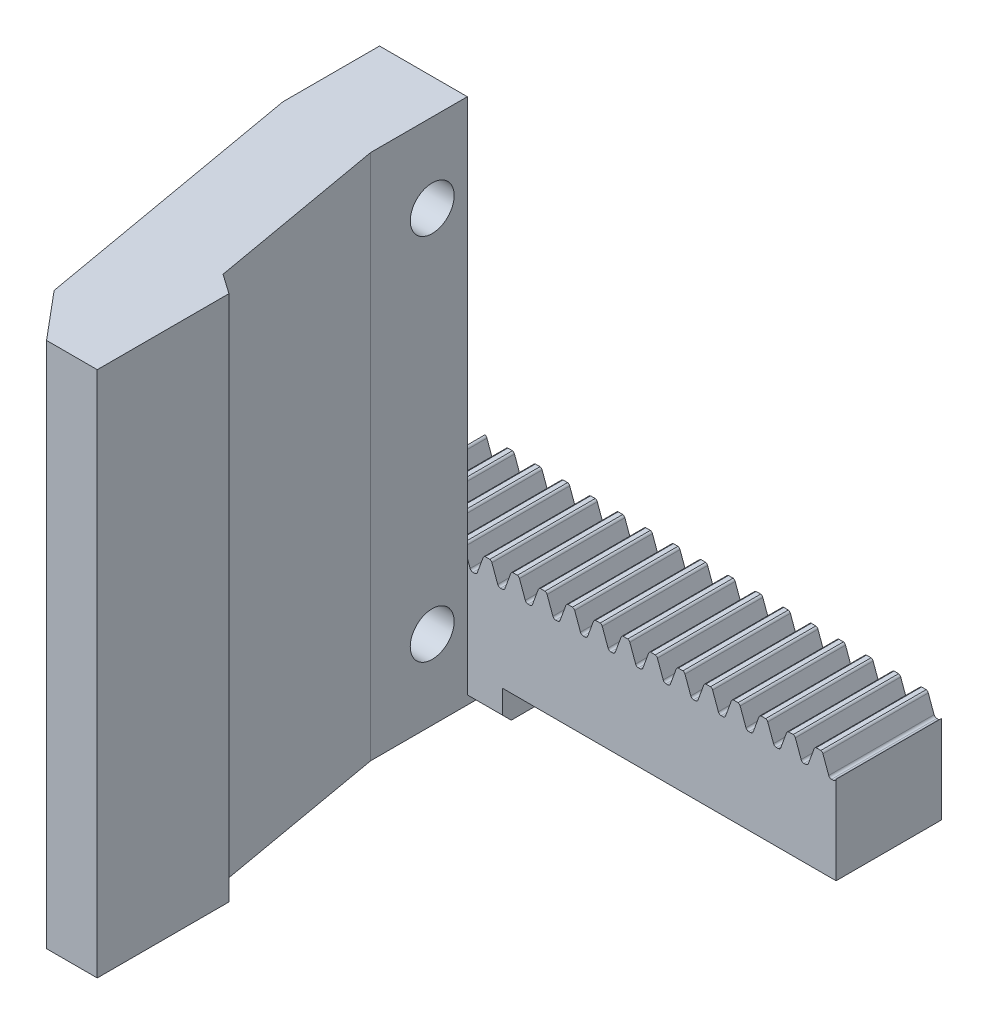
SolidWorks part; units mm, degrees
other "Markup1"
sketch "Sketch7" plane through (-50, -9.66, 16) normal (-0.9886, -0.1404, 0.0537) x (0.0542, 0, 0.9985)
ref_plane "Front Plane" through (0, 0, 0) normal (0, 0, 1) x (1, 0, 0)
ref_plane "Top Plane" through (0, 0, 0) normal (0, 1, 0) x (1, 0, 0)
ref_plane "Right Plane" through (0, 0, 0) normal (1, 0, 0) x (0, 0, -1)
sketch "Sketch1" plane through (0, 0, 0) normal (0, 0, 1) x (1, 0, 0)
  line L0 (-50, 6) -> (-50, -6) construction
  line L1 (-50, -6) -> (50, -6) construction
  line L2 (50, -6) -> (50, 6) construction
  line L4 (0, 6) -> (0, -6) construction
  line L5 (-50, 5) -> (50, 5) construction
  line L6 (-47.5453, 6) -> (-46.7025, 6) construction
  line L7 (-46.7025, 6) -> (-45.8835, 3.75) construction
  line L8 (-47.5453, 6) -> (-48.3643, 3.75) construction
  line L9 (-48.3643, 3.75) -> (-45.8835, 3.75) construction
  line L10 (-47.1239, 6) -> (-47.1239, 3.75) construction
  line L11 (-50, 0) -> (-40.8407, 0) construction
  line L12 (50, 0) -> (40.8407, 0) construction
  point P15 (-43.9823, 6)
  point P16 (-15.5, -6)
  point P17 (-46.3385, 5)
  point P18 (-47.9093, 5)
  point P21 (-0.5, -6)
  dimension "Length" = 100
  dimension "Height" = 12
  dimension "Approximate Number of Teeth" = 31
  dimension "Pressure Angle" = 20
  dimension "Circular Pitch" = 3.1416
  dimension "Addendum" = 1
  dimension "Dedendum" = 1.25
  dimension "Circular Tooth Thickness" = 1.5708
  dimension "Module" = 1
  dimension "Rack Length" = 94.2478
  dimension "D1" = 6.2832
sketch "Sketch2" plane through (0, 0, 0) normal (1, 0, 0) x (0, 0, -1)
  line L0 (-6, 0) -> (6, 0) construction
  dimension "Face Width" = 12
sketch "Sketch3" plane through (0, 0, 0) normal (0, 0, 1) x (1, 0, 0)
  line L1 (-50, 6) -> (50, 6)
  line L2 (-50, 6) -> (-50, -6)
  line L3 (-50, -6) -> (50, -6)
  line L4 (50, 6) -> (50, -6)
extrude "Boss-Extrude1" add sketch "Sketch3" against normal up to vertex (6 mm away) and the other way up to vertex (6 mm away) up to point (0, 0, -6) other way up to point (0, 0, 6)
sketch "Sketch4" plane through (0, 0, 0) normal (0, 0, 1) x (1, 0, 0)
  line L0 (-47.1239, 6) -> (-43.9823, 6) construction
  line L9 (-45.5531, 6) -> (-45.5531, 3.75)
  line L10 (-45.5531, 3.75) -> (-45.8835, 3.75)
  line L11 (-45.8835, 3.75) -> (-46.7025, 6)
  line L12 (-46.7025, 6) -> (-45.5531, 6)
  line L13 (-47.5453, 6) -> (-48.3643, 3.75)
  line L14 (-48.3643, 3.75) -> (-48.6947, 3.75)
  line L15 (-48.6947, 3.75) -> (-48.6947, 6)
  line L16 (-48.6947, 6) -> (-47.5453, 6)
  line L17 (50, 6) -> (-50, 6) construction
  line L18 (-47.5453, 6) -> (-47.3104, 6)
  line L19 (-46.9374, 6) -> (-46.7025, 6)
  arc A0 (-48.5992, 3.75) -> (-48.2839, 3.9708) centre (-48.5992, 4.0855) ccw
  arc A1 (-45.9639, 3.9708) -> (-45.6486, 3.75) centre (-45.6486, 4.0855) ccw
  arc A2 (-47.6257, 5.7792) -> (-47.3104, 6) centre (-47.3104, 5.6645) cw
  arc A3 (-46.9374, 6) -> (-46.6221, 5.7792) centre (-46.9374, 5.6645) cw
  dimension "D1" = 0.3355
extrude "Cut-Extrude1" cut sketch "Sketch4" against normal through all both and the other way through all contours L14 A0 L13 L16 L15 | L13 A2 L18 | L19 A3 L11 | L11 A1 L10 L9 L12 region at (-45.9615, 5.0903, 0) region at (-46.7355, 5.9529, 0) region at (-47.5123, 5.9529, 0) region at (-48.2863, 5.0903, 0)
pattern_linear "LPattern1" count 32 spacing 3.1416 along (1, 0, 0) count 2 spacing 3.1416 along (-1, 0, 0) of "Cut-Extrude1"
sketch "Drawing Refernce 1" plane through (0, 0, 6) normal (0, 0, 1) x (1, 0, 0)
  line L0 (-50, 0) -> (50, 0) construction
  point P6 (-35, 0)
  point P7 (-27.5, 0)
  point P8 (35, 0)
  dimension "D1" = 15
  dimension "D2" = 22.5
  dimension "D3" = 15
sketch "Sketch5" plane through (0, 0, 6) normal (0, 0, 1) x (1, 0, 0)
  line L0 (2, -6) -> (2, 23.2722) construction
  line L1 (-50, -6) -> (50, -6) construction
  line L2 (-50, 5.9906) -> (-50, -6) construction
  line L8 (2, -6) -> (50.3789, -6)
  line L9 (2, -6) -> (2, 6.3802)
  line L10 (2, 6.3802) -> (50.3789, 6.3802)
  line L11 (50.3789, -6) -> (50.3789, 6.3802)
  dimension "D1" = 52
extrude "Cut-Extrude2" cut sketch "Sketch5" against normal through all
sketch "Sketch6" plane through (0, 0, 6) normal (0, 0, 1) x (1, 0, 0)
  line L0 (-50, -6) -> (2, -6) construction
  line L1 (-50, -9.66) -> (-40, -9.66)
  line L2 (-50, -9.66) -> (-50, 50.34)
  line L3 (-50, 50.34) -> (-40, 50.34)
  line L4 (-40, -9.66) -> (-40, 50.34)
  line L5 (-50, 5.9906) -> (-50, -6) construction
  dimension "D1" = 10
  dimension "D2" = 3.66
  dimension "D3" = 60
extrude "Boss-Extrude2" add sketch "Sketch6" along normal blind 8
sketch "Sketch8" plane through (-50, 0, 0) normal (-1, 0, 0) x (0, 0, 1)
  line L1 (14, 50.34) -> (14, -9.66) construction
  line L2 (14, -9.66) -> (6, -9.66) construction
  line L3 (14, 50.34) -> (6, 50.34) construction
  circle A0 centre (10, 41.34) radius 2.5
  circle A1 centre (10, -0.66) radius 2.5
  dimension "D1" = 5
  dimension "D2" = 5
  dimension "D3" = 4
  dimension "D4" = 4
  dimension "D5" = 9
  dimension "D6" = 9
extrude "Cut-Extrude3" cut sketch "Sketch8" against normal through all
sketch "Sketch9" plane through (0, 0, 14) normal (0, 0, 1) x (1, 0, 0)
  line L0 (-40, -9.66) -> (-40, 50.34) construction
  line L1 (-50, 50.34) -> (-38.86, 50.34)
  line L2 (-50, 50.34) -> (-50, -9.66)
  line L3 (-50, -9.66) -> (-38.86, -9.66)
  line L4 (-38.86, 50.34) -> (-38.86, -9.66)
  dimension "D1" = 1.14
extrude "Boss-Extrude3" add sketch "Sketch9" along normal blind 40
sketch "Sketch10" plane through (0, -9.66, 0) normal (0, -1, 0) x (1, 0, 0)
  line L0 (-50, 44) -> (-38.86, 44) construction
  line L1 (-50, 54) -> (-50, 6) construction
  line L2 (-38.86, 54) -> (-38.86, 14) construction
  line L3 (-50, 54) -> (-38.86, 54) construction
  line L5 (-38.86, 44) -> (-38.86, 14)
  line L6 (-38.86, 14) -> (-40, 14)
  line L7 (-40, 14) -> (-40, 44)
  line L8 (-40, 44) -> (-38.86, 44)
  dimension "D1" = 10
extrude "Cut-Extrude4" cut sketch "Sketch10" against normal through all both
chamfer "Chamfer1" distance 12 angle 45 1 edges at (-45, -6, 6)
sketch "Sketch11" plane through (-50, 0, 0) normal (-1, 0, 0) x (0, 0, 1)
  line L5 (-2.34, -9.66) -> (-6, -6)
  line L6 (-6, -6) -> (-6, 5.9906)
  line L7 (-6, 5.9906) -> (6, 5.9906)
  line L8 (6, 5.9906) -> (6, 50.34)
  line L9 (48.3431, 50.34) -> (54, 44.6831)
  line L10 (54, -4.0031) -> (48.3431, -9.66)
  line L11 (43.5443, -10.137) -> (43.4726, -9.66)
  line L12 (-2.34, -9.66) -> (48.3431, -9.66)
  line L13 (6, 50.34) -> (48.3431, 50.34)
  line L14 (54, 44.6831) -> (54, -4.0031)
  circle M13 centre (10, 41.34) radius 2.5
  circle M14 centre (10, -0.66) radius 2.5
  line M15 (6, 5.9906) -> (-6, 5.9906)
  line M16 (-6, 5.9906) -> (-6, -6)
  line M17 (-6, -6) -> (-2.34, -9.66)
  line M18 (-2.34, -9.66) -> (54, -9.66)
  line M19 (54, -9.66) -> (54, 50.34)
  line M20 (54, 50.34) -> (6, 50.34)
  line M21 (6, 50.34) -> (6, 5.9906)
  dimension "D3" = 8
extrude "Cut-Extrude7" cut sketch "Sketch11" against normal blind 71 flip side to cut contours L10 L9 M19 M20 M21 M15 M16 M17 M18 M14 M13 region at (-50, 19.0116, 28.2195)
sketch "Sketch12" plane through (-40, 0, 0) normal (1, 0, 0) x (0, 0, -1)
  line L0 (-54, 44.6831) -> (-54, -9.66)
  line L1 (-44, 50.34) -> (-6, 50.34) construction
  line L2 (-17, 50.34) -> (-17, -9.66)
  line L3 (-44, -9.66) -> (2.34, -9.66) construction
  line L4 (-54, 50.34) -> (-17, 50.34)
  line L5 (-54, 44.6831) -> (-54, 50.34)
  line L7 (-54, -9.66) -> (-17, -9.66)
extrude "Cut-Extrude8" cut sketch "Sketch12" against normal blind 30 and the other way blind 30
sketch "Sketch13" plane through (0, -9.66, 0) normal (0, -1, 0) x (1, 0, 0)
  line L1 (-40, 17) -> (-36.3987, 37.4238)
  line L5 (-50, 17) -> (-40, 17)
  line L6 (-50, 17) -> (-44.4214, 48.6377)
  line L7 (-50, 17) -> (-50, 54)
  line L8 (-44.4214, 48.6377) -> (-39.9219, 54)
  line L10 (-34.1477, 39) -> (-34.1477, 54)
  line L11 (-34.1477, 54) -> (-39.9219, 54)
  line L12 (-36.3987, 37.4238) -> (-34.1477, 39)
  line M13 (-40, 17) -> (-50, 17)
  dimension "D1" = 80
  dimension "D2" = 80
  dimension "D3" = 150
  dimension "D4" = 7
  dimension "D5" = 37
  dimension "D6" = 15
  dimension "D7" = 135
extrude "Boss-Extrude4" add sketch "Sketch13" against normal blind 60 contours L1 L12 L10 L11 L8 L6 M13 region at (-41.5109, -9.66, 35.2395)
sketch "Sketch14" plane through (-51.3995, 0, 9.0631) normal (-0.9848, 0, 0.1736) x (0.1736, 0, 0.9848)
  line L0 (8.0593, 50.34) -> (8.0593, -9.66)
  line L1 (8.0593, -9.66) -> (40.1851, -9.66)
  line L2 (40.1851, -9.66) -> (40.1851, 50.34)
  line L3 (40.1851, 50.34) -> (8.0593, 50.34)
  line L4 (8.0593, 50.34) -> (9.7709, 48.7542)
  line L5 (9.7709, 48.7542) -> (38.7709, 48.7542)
  line L6 (38.7709, 48.7542) -> (40.1851, 50.34)
  line L7 (38.7709, 48.7542) -> (38.7709, -8.2458)
  line L8 (38.7709, -8.2458) -> (40.1851, -9.66)
  line L9 (38.7709, -8.2458) -> (9.7709, -8.2458)
  line L10 (9.7709, -8.2458) -> (8.0593, -9.66)
  line L11 (9.7709, -8.2458) -> (9.7709, 48.7542)
  dimension "D1" = 29
  dimension "D2" = 57
  dimension "D4" = 45
extrude "Cut-Extrude9" cut sketch "Sketch14" against normal blind 2 contours L11 L9 L7 L5 region at (-47.1849, 20.2542, 32.9652)
chamfer "Chamfer2" distance 4 angle 45 4 edges at (-48.718, -8.2458, 18.5119) (-43.6822, -8.2458, 47.0713) (-48.718, 48.7542, 18.5119) (-43.6822, 48.7542, 47.0713)
sketch "Sketch17" plane through (0, -6, 0) normal (0, -1, 0) x (1, 0, 0)
  line L0 (-40, -6) -> (-36, -6)
  line L1 (-36, -6) -> (-36, 6)
  line L2 (-40, 6) -> (2, 6) construction
  line L3 (-36, 6) -> (-40, 6)
  line L4 (-40, 6) -> (-40, -6)
  line L6 (-40, -6) -> (2, -6) construction
  point P3 (0, 0)
extrude "Boss-Extrude5" add sketch "Sketch17" along normal blind 3.66
ref_plane "Plane1" through (2, -6, -6) normal (-1, 0, 0) x (0, 0, 1)
ref_plane "Plane2" through (-40, -6, -6) normal (1, 0, 0) x (0, 0, -1)
sketch "Sketch20" plane through (0, -9.66, 0) normal (0, -1, 0) x (1, 0, 0)
  line L0 (-40, -6) -> (-50, -6)
  line L1 (-50, -6) -> (-50, -2.34)
  line L2 (-50, -2.34) -> (-40, -2.34)
  line L3 (-40, -2.34) -> (-40, -6)
extrude "Boss-Extrude6" add sketch "Sketch20" against normal blind 5.66
chamfer "Chamfer8" distance 1 angle 45 1 edges at (-38, -9.66, 6)
equation "\"Diametral Pitch\"= 1 / \"Module\""
equation "\"Pressure Angle\"=20"
equation "\"Dedendum\"= 1.25 / \"Diametral Pitch\""
equation "\"Addendum\"= 1 / \"Diametral Pitch\""
equation "\"WorkingDepth\"= 2 / \"Diametral Pitch\""
equation "\"WholeDepth\"= 2.25 / \"Diametral Pitch\""
equation "\"Clearance\"= 0.25 / \"Diametral Pitch\""
equation "\"ToothThickness\"= ( pi / 2 ) / \"Diametral Pitch\""
equation "\"CircularPitch\"= pi / \"Diametral Pitch\""
equation "\"Fillet\"= \"Clearance\" * cos ( \"Pressure Angle\" ) * tan ( ( 90 + \"Pressure Angle\" ) / 2 )"
equation "\"Module\"= 1"
equation "\"Addendum@Sketch1\"=\"Addendum\""
equation "\"Pressure Angle@Sketch1\"=\"Pressure Angle\""
equation "\"Dedendum@Sketch1\"=\"Dedendum\""
equation "\"Circular Pitch@Sketch1\"=\"CircularPitch\""
equation "\"Circular Tooth Thickness@Sketch1\"=\"ToothThickness\""
equation "\"Module@Sketch1\"=\"Module\""
equation "\"Approximate Number of Teeth@Sketch1\" = int ( \"Length@Sketch1\" /  ( 2 * \"Circular Tooth Thickness@Sketch1\" )  ) "
equation "\"Rack Length@Sketch1\" = \"Circular Pitch@Sketch1\" *  ( \"Approximate Number of Teeth@Sketch1\" - 1 ) "
equation "\"D3@LPattern1\"=\"CircularPitch\""
equation "\"D1@LPattern1\"=\"Approximate Number of Teeth@Sketch1\"+1"
equation "\"D1@Sketch1\"=\"Circular Pitch@Sketch1\"*2"
equation "\"D1@Sketch4\"=\"Fillet\""
equation "\"D4@LPattern1\"=\"CircularPitch\""
equation "\"D2@Drawing Refernce 1\"=\"D1@Drawing Refernce 1\"*1.5"
equation "\"D3@Drawing Refernce 1\"=\"D1@Drawing Refernce 1\""
